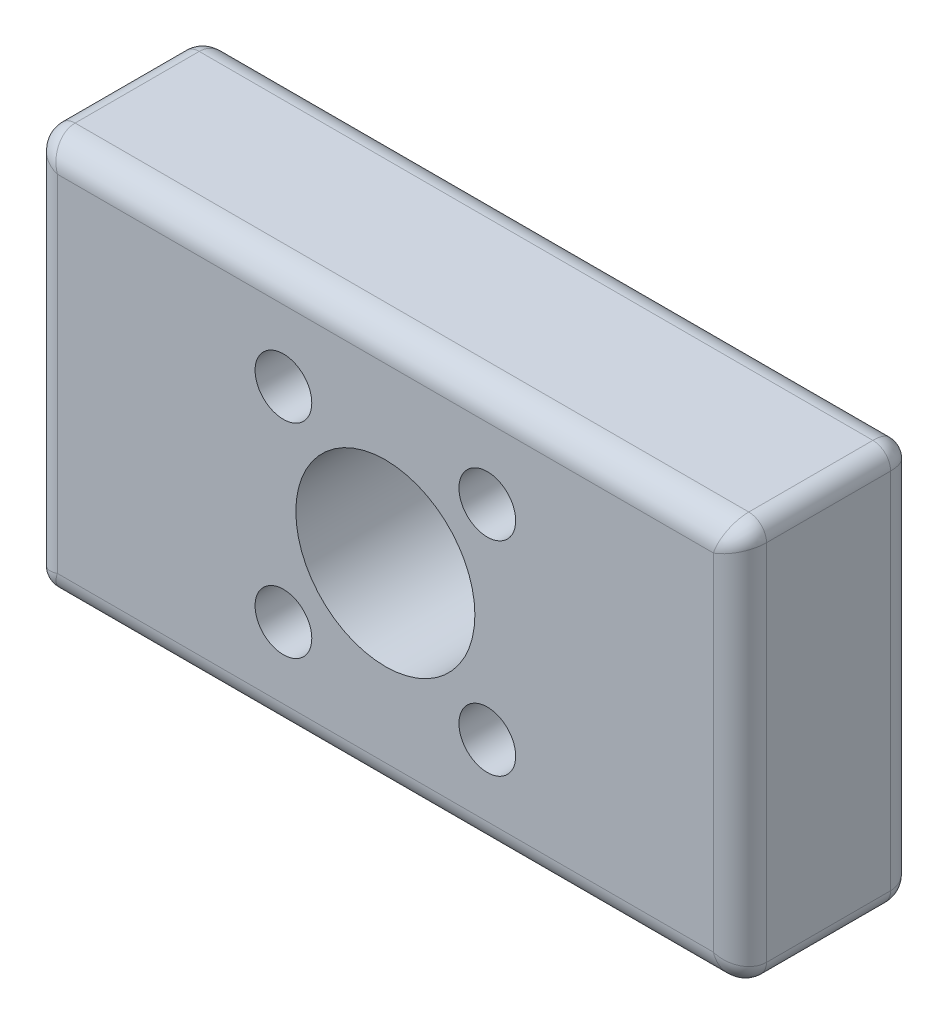
SolidWorks part; units mm, degrees
ref_plane "Front Plane" through (0, 0, 0) normal (0, 0, 1) x (1, 0, 0)
ref_plane "Top Plane" through (0, 0, 0) normal (0, 1, 0) x (1, 0, 0)
ref_plane "Right Plane" through (0, 0, 0) normal (1, 0, 0) x (0, 0, -1)
sketch "Sketch1" plane through (0, 0, 0) normal (0, 0, 1) x (1, 0, 0)
  circle A0 centre (0, 0) radius 5.05
  circle A1 centre (0, 0) radius 11.25
  dimension "D1" = 10.1
  dimension "D3" = 22.5
extrude "Boss-Extrude1" add sketch "Sketch1" along normal blind 10
sketch "Sketch2" plane through (0, 0, 10) normal (0, 0, 1) x (1, 0, 0)
  line L1 (-19, -11.25) -> (19, -11.25)
  line L2 (-20, -10.25) -> (-20, 10.25)
  line L3 (-19, 11.25) -> (19, 11.25)
  line L4 (20, -10.25) -> (20, 10.25)
  line L5 (-20, -11.25) -> (20, 11.25) construction
  line L6 (-20, 11.25) -> (20, -11.25) construction
  circle A0 centre (0, 0) radius 11.25 construction
  arc A1 (-20, -10.25) -> (-19, -11.25) centre (-19, -10.25) ccw
  arc A2 (19, -11.25) -> (20, -10.25) centre (19, -10.25) ccw
  arc A3 (20, 10.25) -> (19, 11.25) centre (19, 10.25) ccw
  arc A4 (-19, 11.25) -> (-20, 10.25) centre (-19, 10.25) ccw
  circle A5 centre (0, 0) radius 5.05
  point P0 (0, 0)
  dimension "D2" = 1
  dimension "D1" = 40
  dimension "D3" = 22.5
extrude "Boss-Extrude2" add sketch "Sketch2" against normal blind 10
sketch "Sketch3" plane through (0, 0, 10) normal (0, 0, 1) x (1, 0, 0)
  line L1 (-5.75, 5.75) -> (5.75, 5.75) construction
  line L2 (-5.75, 5.75) -> (-5.75, -5.75) construction
  line L3 (-5.75, -5.75) -> (5.75, -5.75) construction
  line L4 (5.75, 5.75) -> (5.75, -5.75) construction
  line L5 (-5.75, 5.75) -> (5.75, -5.75) construction
  line L6 (-5.75, -5.75) -> (5.75, 5.75) construction
  circle A1 centre (-5.75, 5.75) radius 1.6
  circle A2 centre (5.75, 5.75) radius 1.6
  circle A3 centre (5.75, -5.75) radius 1.6
  circle A4 centre (-5.75, -5.75) radius 1.6
  point P0 (0, 0)
  dimension "D2" = 3.2
  dimension "D1" = 11.5
extrude "Cut-Extrude1" cut sketch "Sketch3" against normal blind 10
sketch "Sketch4" plane through (0, 0, 10) normal (0, 0, 1) x (1, 0, 0)
  circle A0 centre (0, 0) radius 11.25
  dimension "D1" = 22.5
sketch "Sketch5" plane through (0, 0, 0) normal (0, 0, -1) x (-1, 0, 0)
  line L0 (-2.7701, 4.653) -> (2.7701, 4.653) construction
  line L1 (-2.7701, 4.653) -> (-3.31, 7.7822)
  line L2 (-3.31, 7.7822) -> (-6.29, 8.8792)
  line L3 (-6.29, 8.8792) -> (-8.7299, 6.847)
  line L4 (-8.7299, 6.847) -> (-8.19, 3.7178)
  line L5 (-8.19, 3.7178) -> (-5.21, 2.6208)
  line L6 (-5.21, 2.6208) -> (-2.7701, 4.653)
  line L7 (5.21, -2.6208) -> (2.7701, -4.653)
  line L8 (2.7701, -4.653) -> (3.31, -7.7822)
  line L9 (3.31, -7.7822) -> (6.29, -8.8792)
  line L10 (6.29, -8.8792) -> (8.7299, -6.847)
  line L11 (8.7299, -6.847) -> (8.19, -3.7178)
  line L12 (8.19, -3.7178) -> (5.21, -2.6208)
  line L13 (5.21, 2.6208) -> (8.19, 3.7178)
  line L14 (8.19, 3.7178) -> (8.7299, 6.847)
  line L15 (8.7299, 6.847) -> (6.29, 8.8792)
  line L16 (6.29, 8.8792) -> (3.31, 7.7822)
  line L17 (3.31, 7.7822) -> (2.7701, 4.653)
  line L18 (2.7701, 4.653) -> (5.21, 2.6208)
  line L19 (5.21, 2.6208) -> (5.21, -2.6208) construction
  line L20 (-2.7701, -4.653) -> (-5.21, -2.6208)
  line L21 (-5.21, -2.6208) -> (-8.19, -3.7178)
  line L22 (-8.19, -3.7178) -> (-8.7299, -6.847)
  line L23 (-8.7299, -6.847) -> (-6.29, -8.8792)
  line L24 (-6.29, -8.8792) -> (-3.31, -7.7822)
  line L25 (-3.31, -7.7822) -> (-2.7701, -4.653)
  line L26 (2.7701, -4.653) -> (-2.7701, -4.653) construction
  line L27 (-5.21, -2.6208) -> (-5.21, 2.6208) construction
  circle A0 centre (-5.75, 5.75) radius 2.75 construction
  circle A1 centre (5.75, -5.75) radius 2.75 construction
  circle A2 centre (5.75, 5.75) radius 2.75 construction
  circle A3 centre (-5.75, -5.75) radius 2.75 construction
  dimension "D1" = 5.5
extrude "Cut-Extrude2" cut sketch "Sketch5" against normal blind 3
fillet "Fillet1" radius 1.5 16 edges at (-19.7071, -10.9571, 10) (-20, 0, 10) (-19.7071, 10.9571, 10) (0, 11.25, 10) (19.7071, 10.9571, 10) (20, 0, 10) (19.7071, -10.9571, 10) (-19.7071, -10.9571, 0) (-20, 0, 0) (-19.7071, 10.9571, 0) (0, 11.25, 0) (19.7071, 10.9571, 0) (20, 0, 0) (19.7071, -10.9571, 0) (0, -11.25, 10) (0, -11.25, 0)
